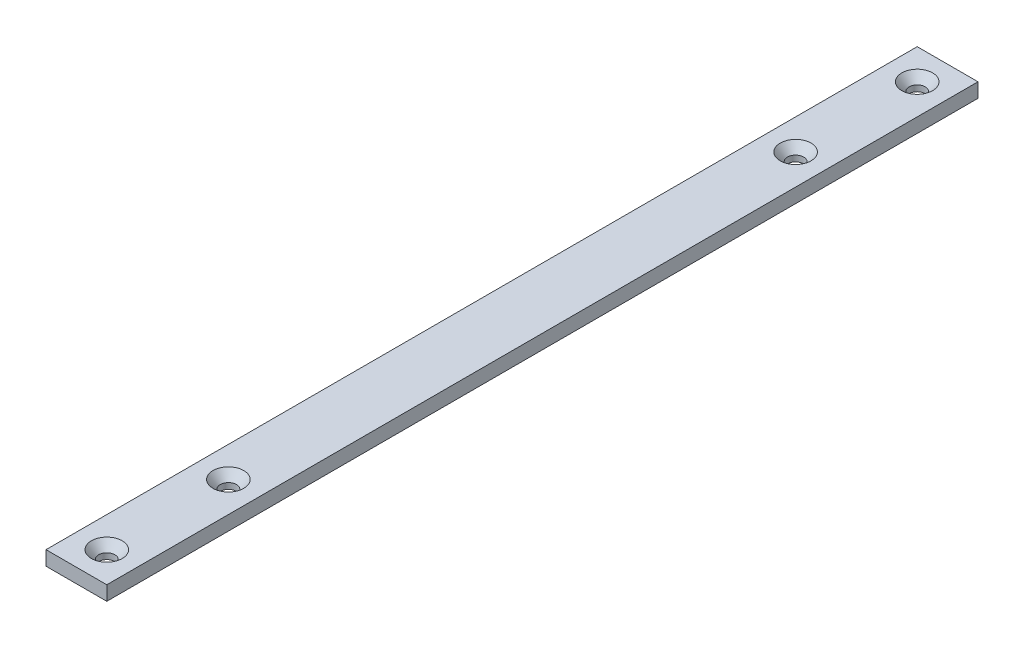
SolidWorks part; units mm, degrees
ref_plane "Front Plane" through (0, 0, 0) normal (0, 0, 1) x (1, 0, 0)
ref_plane "Top Plane" through (0, 0, 0) normal (0, 1, 0) x (1, 0, 0)
ref_plane "Right Plane" through (0, 0, 0) normal (1, 0, 0) x (0, 0, -1)
sketch "Sketch1" plane through (0, 0, 0) normal (0, 0, 1) x (1, 0, 0)
  line L0 (0, 3.9688) -> (0, -3.9688)
  line L1 (-12.7, 0) -> (12.7, 0) construction
  point P6 (0, 0)
  dimension "Width" = 25.4
  dimension "Thk" = 7.9375
sketch "Sketch2" plane through (0, 0, 0) normal (1, 0, 0) x (0, 0, -1)
  line L0 (152.4, 0) -> (-152.4, 0)
  point P4 (0, 0)
  dimension "Length" = 304.8
sketch "Sketch3" plane through (0, 0, 0) normal (0, 0, 1) x (1, 0, 0)
  line L5 (12.7, -3) -> (-12.7, -3)
  line L6 (12.7, -3) -> (12.7, 3)
  line L7 (12.7, 3) -> (-12.7, 3)
  line L8 (-12.7, -3) -> (-12.7, 3)
  line L9 (12.7, -3) -> (-12.7, 3) construction
  line L10 (12.7, 3) -> (-12.7, -3) construction
  point P0 (0, 0)
  point P1 (0, 0)
  dimension "D1" = 25.4
  dimension "D2" = 6
extrude "Boss-Extrude1" add sketch "Sketch3" along normal mid plane 364
sketch "Sketch5" plane through (0, 3, 0) normal (0, 1, 0) x (1, 0, 0)
  line L2 (12.7, 0) -> (-12.7, 0) construction
  line L3 (12.7, -182) -> (12.7, 182) construction
  line L4 (12.7, 182) -> (-12.7, 182) construction
  circle A0 centre (0, 169.3) radius 3.5
  circle A1 centre (0, -169.3) radius 3.5
  circle A2 centre (0, 118.5) radius 3.5
  circle A3 centre (0, -118.5) radius 3.5
  point P14 (0, 0)
  dimension "D1" = 7
  dimension "D2" = 12.7
  dimension "D3" = 12.7
  dimension "D4" = 7
  dimension "D5" = 50.8
hole_wizard "CSK for 1/4 Flat Head Machine Screw1" positions "Sketch7" profile "Sketch8" countersink size "1/4" standard "ANSI Inch" end condition through all
sketch "Sketch7" plane through (0, 3, 0) normal (0, 1, 0) x (1, 0, 0)
  point P0 (0, 169.3)
  point P3 (0, -169.3)
  point P6 (0, 118.5)
  point P9 (0, -118.5)
sketch "Sketch8" plane through (0, 3, -169.3) normal (1, 0, 0) x (0, 0, 1)
  line L0 (0, 0) -> (0, 6)
  line L1 (0, 6) -> (3.3782, 6)
  line L2 (3.3782, 6) -> (3.3782, 3.5209)
  line L3 (3.3782, 3.5209) -> (6.4389, 0)
  line L5 (6.4389, 0) -> (0, 0)
  line L6 (-3.3782, 3.5209) -> (-6.4389, 0) construction
  line L11 (0, -6.35) -> (0, 107.95) construction
  dimension "Thru Hole Dia." = 6.7564
  dimension "Thru Hole Depth" = 6
  dimension "Near C'Sink Dia." = 12.8778
  dimension "Near C'Sink Angle" = 82
